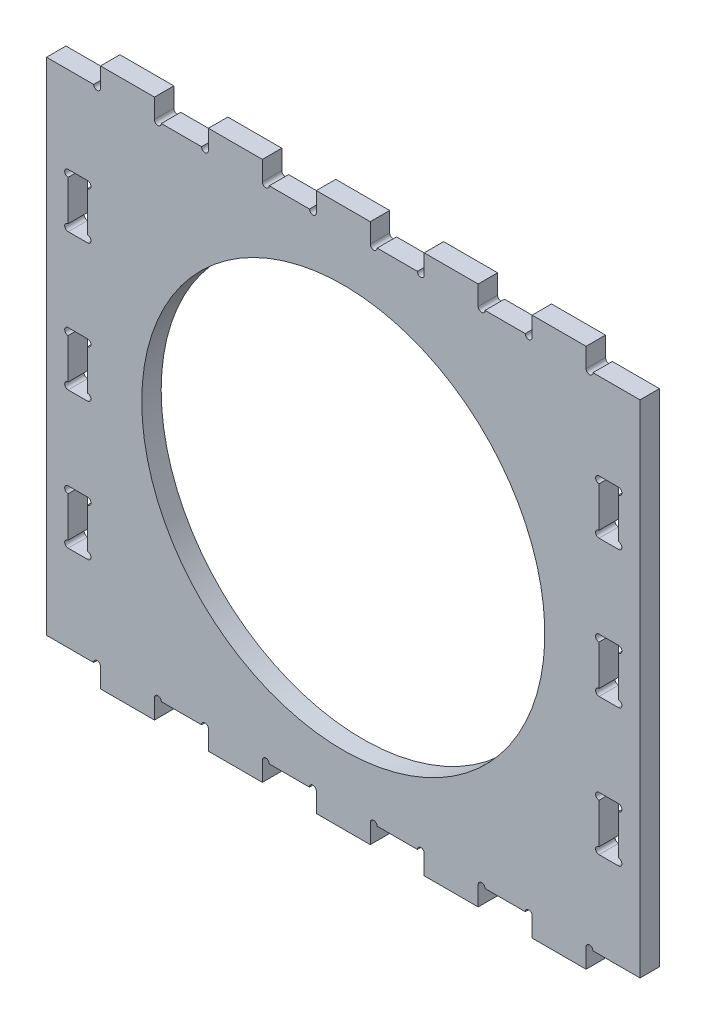
SolidWorks part; units mm, degrees
ref_plane "Piano frontale" through (0, 0, 0) normal (0, 0, 1) x (1, 0, 0)
ref_plane "Piano superiore" through (0, 0, 0) normal (0, 1, 0) x (1, 0, 0)
ref_plane "Piano destro" through (0, 0, 0) normal (1, 0, 0) x (0, 0, -1)
sketch "Model" plane through (0, 0, 0) normal (0, 0, 1) x (1, 0, 0)
  line L0 (-255, 145.65) -> (-255, 108.35)
  line L1 (-255, 102) -> (-237, 102)
  line L2 (-237, 145.65) -> (-237, 108.35)
  line L3 (-255, 152) -> (-237, 152)
  line L4 (237, 145.65) -> (237, 108.35)
  line L5 (255, 102) -> (237, 102)
  line L6 (255, 145.65) -> (255, 108.35)
  line L7 (255, 152) -> (237, 152)
  line L8 (0, 0) -> (504.1303, 0) construction
  line L9 (-275, -232) -> (-275, 232)
  line L10 (-25, 250) -> (25, 250)
  line L11 (-225, 250) -> (-225, 232)
  line L12 (-68.65, 232) -> (-31.35, 232)
  line L13 (-175, 232) -> (-175, 250)
  line L14 (31.35, 232) -> (68.65, 232)
  line L15 (-125, 250) -> (-125, 232)
  line L16 (75, 250) -> (125, 250)
  line L17 (-75, 232) -> (-75, 250)
  line L18 (131.35, 232) -> (168.65, 232)
  line L19 (-25, 250) -> (-25, 232)
  line L20 (175, 250) -> (225, 250)
  line L21 (25, 232) -> (25, 250)
  line L22 (231.35, 232) -> (275, 232)
  line L23 (75, 250) -> (75, 232)
  line L24 (-275, 232) -> (-231.35, 232)
  line L25 (125, 232) -> (125, 250)
  line L26 (231.35, -232) -> (275, -232)
  line L27 (175, 250) -> (175, 232)
  line L28 (-275, -232) -> (-231.35, -232)
  line L29 (225, 232) -> (225, 250)
  line L30 (-125, -250) -> (-75, -250)
  line L31 (275, 232) -> (275, -232)
  line L32 (-168.65, -232) -> (-131.35, -232)
  line L33 (-225, -250) -> (-175, -250)
  line L34 (225, -232) -> (225, -250)
  line L35 (175, -250) -> (175, -232)
  line L36 (125, -232) -> (125, -250)
  line L37 (75, -250) -> (75, -232)
  line L38 (25, -232) -> (25, -250)
  line L39 (175, -250) -> (225, -250)
  line L40 (-25, -250) -> (-25, -232)
  line L41 (131.35, -232) -> (168.65, -232)
  line L42 (-75, -232) -> (-75, -250)
  line L43 (75, -250) -> (125, -250)
  line L44 (-125, -250) -> (-125, -232)
  line L45 (31.35, -232) -> (68.65, -232)
  line L46 (-175, -232) -> (-175, -250)
  line L47 (-68.65, -232) -> (-31.35, -232)
  line L48 (-225, -250) -> (-225, -232)
  line L49 (-25, -250) -> (25, -250)
  line L52 (237, -18.65) -> (237, 18.65)
  line L53 (255, -25) -> (237, -25)
  line L54 (255, -18.65) -> (255, 18.65)
  line L55 (255, 25) -> (237, 25)
  line L56 (237, -145.65) -> (237, -108.35)
  line L57 (255, -152) -> (237, -152)
  line L58 (255, -145.65) -> (255, -108.35)
  line L59 (255, -102) -> (237, -102)
  line L60 (-255, -18.65) -> (-255, 18.65)
  line L61 (-255, -25) -> (-237, -25)
  line L62 (-237, -18.65) -> (-237, 18.65)
  line L63 (-255, 25) -> (-237, 25)
  line L64 (-255, -145.65) -> (-255, -108.35)
  line L65 (-255, -152) -> (-237, -152)
  line L66 (-237, -145.65) -> (-237, -108.35)
  line L67 (-255, -102) -> (-237, -102)
  line L69 (-225, 250) -> (-175, 250)
  line L70 (-168.65, 232) -> (-131.35, 232)
  line L71 (-125, 250) -> (-75, 250)
  arc A0 (-255, 152) -> (-255, 145.65) centre (-255, 148.825) ccw
  arc A1 (-255, 108.35) -> (-255, 102) centre (-255, 105.175) ccw
  arc A2 (-237, 102) -> (-237, 108.35) centre (-237, 105.175) ccw
  arc A3 (-237, 145.65) -> (-237, 152) centre (-237, 148.825) ccw
  arc A4 (237, 152) -> (237, 145.65) centre (237, 148.825) ccw
  arc A5 (237, 108.35) -> (237, 102) centre (237, 105.175) ccw
  arc A6 (255, 102) -> (255, 108.35) centre (255, 105.175) ccw
  arc A7 (255, 145.65) -> (255, 152) centre (255, 148.825) ccw
  arc A8 (-131.35, 232) -> (-125, 232) centre (-128.175, 232) ccw
  arc A9 (-175, 232) -> (-168.65, 232) centre (-171.825, 232) ccw
  arc A10 (-31.35, 232) -> (-25, 232) centre (-28.175, 232) ccw
  arc A11 (-75, 232) -> (-68.65, 232) centre (-71.825, 232) ccw
  arc A12 (68.65, 232) -> (75, 232) centre (71.825, 232) ccw
  arc A13 (25, 232) -> (31.35, 232) centre (28.175, 232) ccw
  arc A14 (168.65, 232) -> (175, 232) centre (171.825, 232) ccw
  arc A15 (125, 232) -> (131.35, 232) centre (128.175, 232) ccw
  arc A16 (-231.35, -232) -> (-225, -232) centre (-228.175, -232) cw
  arc A17 (225, 232) -> (231.35, 232) centre (228.175, 232) ccw
  arc A18 (225, -232) -> (231.35, -232) centre (228.175, -232) cw
  arc A19 (125, -232) -> (131.35, -232) centre (128.175, -232) cw
  arc A20 (168.65, -232) -> (175, -232) centre (171.825, -232) cw
  arc A21 (25, -232) -> (31.35, -232) centre (28.175, -232) cw
  arc A22 (68.65, -232) -> (75, -232) centre (71.825, -232) cw
  arc A23 (-75, -232) -> (-68.65, -232) centre (-71.825, -232) cw
  arc A24 (-31.35, -232) -> (-25, -232) centre (-28.175, -232) cw
  arc A25 (-175, -232) -> (-168.65, -232) centre (-171.825, -232) cw
  arc A26 (-131.35, -232) -> (-125, -232) centre (-128.175, -232) cw
  circle A27 centre (0, 0) radius 186.7665
  arc A28 (237, -18.65) -> (237, -25) centre (237, -21.825) ccw
  arc A29 (255, -25) -> (255, -18.65) centre (255, -21.825) ccw
  arc A30 (255, 18.65) -> (255, 25) centre (255, 21.825) ccw
  arc A31 (237, 25) -> (237, 18.65) centre (237, 21.825) ccw
  arc A32 (237, -145.65) -> (237, -152) centre (237, -148.825) ccw
  arc A33 (255, -152) -> (255, -145.65) centre (255, -148.825) ccw
  arc A34 (255, -108.35) -> (255, -102) centre (255, -105.175) ccw
  arc A35 (237, -102) -> (237, -108.35) centre (237, -105.175) ccw
  arc A36 (-255, -18.65) -> (-255, -25) centre (-255, -21.825) ccw
  arc A37 (-237, -25) -> (-237, -18.65) centre (-237, -21.825) ccw
  arc A38 (-237, 18.65) -> (-237, 25) centre (-237, 21.825) ccw
  arc A39 (-255, 25) -> (-255, 18.65) centre (-255, 21.825) ccw
  arc A40 (-255, -145.65) -> (-255, -152) centre (-255, -148.825) ccw
  arc A41 (-237, -152) -> (-237, -145.65) centre (-237, -148.825) ccw
  arc A42 (-237, -108.35) -> (-237, -102) centre (-237, -105.175) ccw
  arc A43 (-255, -102) -> (-255, -108.35) centre (-255, -105.175) ccw
  arc A45 (-231.35, 232) -> (-225, 232) centre (-228.175, 232) ccw
  arc A46 (268.65, 232) -> (275, 232) centre (271.825, 232) ccw [skipped]
  dimension "D2" = 500
  dimension "D1" = 6
extrude "Estrusione-Estrusione1" add sketch "Model" along normal blind 18 contours L70 A8 L15 L71 L17 A11 L12 A10 L19 L10 L21 A13 L14 A12 L23 L16 L25 A15 L18 A14 L27 L20 L29 A17 L22 L31 L26 A18 L34 L39 L35 A20 L41 A19 L36 L43 L37 A22 L45 A21 L38 L49 L40 A24 L47 A23 L42 L30 L44 A26 L32 A25 L46 L33 L48 A16 L28 L9 L24 A45 L11 L69 L13 A9
extrude "Taglio-Estrusione1" cut sketch "Model<3>" along normal blind 47 contours L2 A2 L1 A1 L0 A0 L3 A3
sketch "Model<3>" plane through (0, 0, 0) normal (0, 0, 1) x (1, 0, 0) same geometry as "Model"
extrude "Taglio-Estrusione2" cut sketch "Model<4>" along normal blind 32 contours L62 A38 L63 A39 L60 A36 L61 A37
sketch "Model<4>" plane through (0, 0, 0) normal (0, 0, 1) x (1, 0, 0) same geometry as "Model"
extrude "Taglio-Estrusione3" cut sketch "Model<5>" along normal blind 50 contours L66 A42 L67 A43 L64 A40 L65 A41
sketch "Model<5>" plane through (0, 0, 0) normal (0, 0, 1) x (1, 0, 0) same geometry as "Model"
extrude "Taglio-Estrusione4" cut sketch "Model<6>" along normal blind 44 contours L4 A5 L5 A6 L6 A7 L7 A4
sketch "Model<6>" plane through (0, 0, 0) normal (0, 0, 1) x (1, 0, 0) same geometry as "Model"
extrude "Taglio-Estrusione5" cut sketch "Model<7>" along normal blind 38 contours L54 A30 L55 A31 L52 A28 L53 A29
sketch "Model<7>" plane through (0, 0, 0) normal (0, 0, 1) x (1, 0, 0) same geometry as "Model"
extrude "Taglio-Estrusione6" cut sketch "Model<10>" along normal blind 44 contours L56 A35 L59 A34 L58 A33 L57 A32
sketch "Model<10>" plane through (0, 0, 0) normal (0, 0, 1) x (1, 0, 0) same geometry as "Model"
extrude "Taglio-Estrusione7" cut sketch "Model<11>" along normal blind 91 contours A27
sketch "Model<11>" plane through (0, 0, 0) normal (0, 0, 1) x (1, 0, 0) same geometry as "Model"
